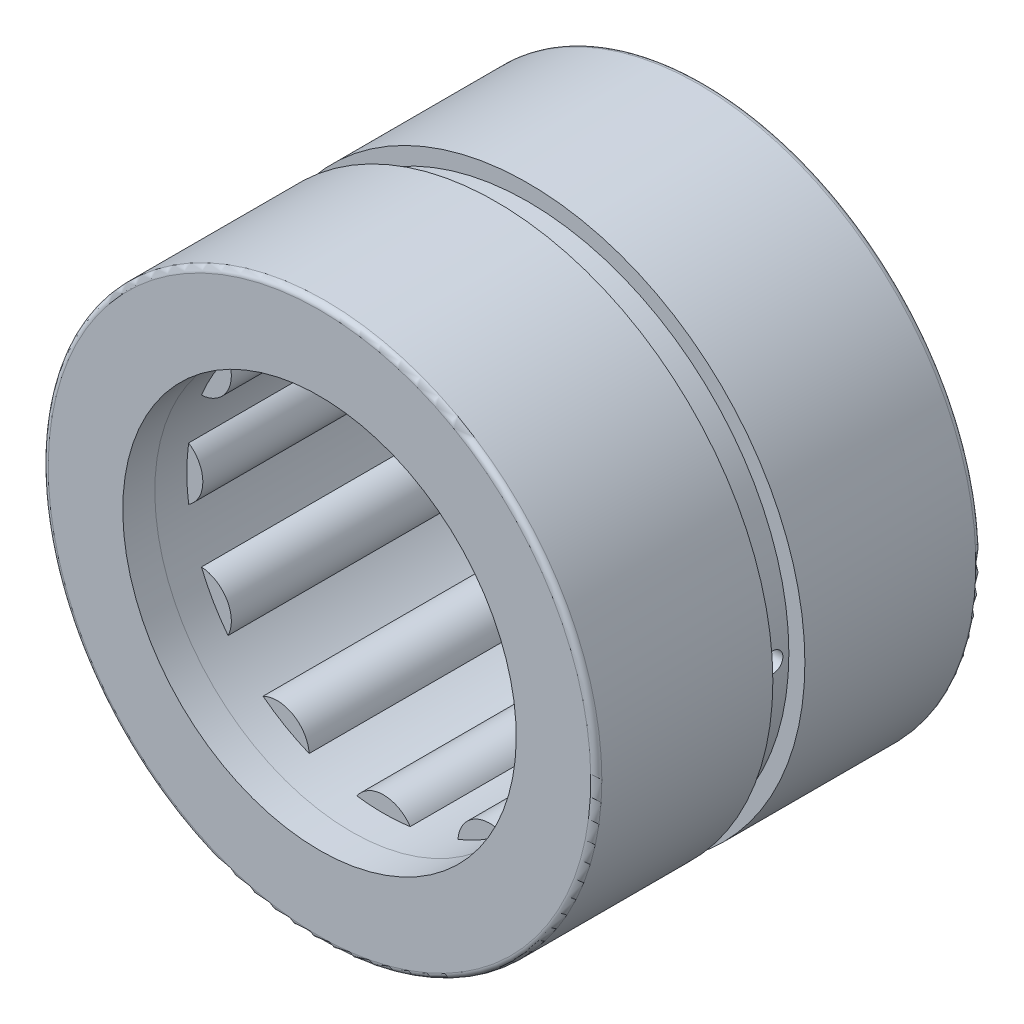
SolidWorks part; units mm, degrees
material "Plain Carbon Steel"
ref_plane "Front Plane" through (0, 0, 0) normal (0, 0, 1) x (1, 0, 0)
ref_plane "Top Plane" through (0, 0, 0) normal (0, 1, 0) x (1, 0, 0)
ref_plane "Right Plane" through (0, 0, 0) normal (1, 0, 0) x (0, 0, -1)
sketch "Sketch1" plane through (0, 0, 0) normal (1, 0, 0) x (0, 0, -1)
  line L0 (-8, 0) -> (8, 0) construction
  line L1 (0, 0) -> (0, 11.5) construction
  line L2 (-8, 0) -> (-8, 11.5) construction
  line L3 (-8, 11.5) -> (8, 11.5)
  line L4 (8, 11.5) -> (8, 0) construction
  line L5 (8, 0) -> (6.6693, 0) construction
  line L6 (6.6693, 0) -> (6.6693, 10.1693) construction
  line L7 (6.6693, 10.1693) -> (-6.6693, 10.1693)
  line L8 (-6.6693, 10.1693) -> (-6.6693, 0) construction
  line L9 (-6.6693, 0) -> (-8, 0) construction
  line L10 (-8, 11.5) -> (-8, 8.1733)
  line L11 (-8, 8.1733) -> (-6.6693, 8.1733)
  line L12 (-6.6693, 8.1733) -> (-6.6693, 10.1693)
  line L13 (6.6693, 11.5) -> (6.6693, 10.1693) construction
  line L14 (6.6693, 10.1693) -> (6.6693, 8.1733)
  line L15 (6.6693, 8.1733) -> (8, 8.1733)
  line L16 (8, 8.1733) -> (8, 11.5)
  line L17 (6.6693, 10.1693) -> (6.6693, 8.8387) construction
  line L18 (6.6693, 8.8387) -> (6.6693, 7.508) construction
  line L19 (6.6693, -10.1693) -> (6.6693, -8.8387) construction
  line L20 (6.6693, -11.5) -> (6.6693, -10.1693) construction
  line L21 (8, -8.1733) -> (8, -11.5) construction
  line L22 (6.6693, -8.1733) -> (8, -8.1733) construction
  line L23 (6.6693, -10.1693) -> (6.6693, -8.1733) construction
  line L24 (-6.6693, -8.1733) -> (-6.6693, -10.1693) construction
  line L25 (-8, -8.1733) -> (-6.6693, -8.1733) construction
  line L26 (-8, -11.5) -> (-8, -8.1733) construction
  line L27 (6.6693, -10.1693) -> (-6.6693, -10.1693) construction
  line L28 (-8, -11.5) -> (8, -11.5) construction
  point P5 (0, 7.508)
  dimension "Width" = 16
  dimension "OD" = 23
  dimension "Shaft Dia" = 15.016
revolve "Revolve1" add sketch "Sketch1" angle 360 about L0
sketch "Sketch2" plane through (0, 0, 0) normal (1, 0, 0) x (0, 0, -1)
  line L0 (6.6693, 10.1693) -> (-6.6693, 10.1693) construction
  line L1 (-5.3387, 8.8387) -> (5.3387, 8.8387) construction
  line L2 (-5.3387, 8.8387) -> (-5.3387, 10.1693) construction
  line L3 (-5.3387, 10.1693) -> (5.3387, 10.1693)
  line L4 (5.3387, 8.8387) -> (5.3387, 10.1693) construction
  line L5 (6.6693, 8.1733) -> (8, 8.1733) construction
  line L6 (-6.6693, 8.8387) -> (-5.3387, 8.8387) construction
  line L7 (5.3387, 8.8387) -> (6.6693, 8.8387) construction
  line L8 (-8, 8.1733) -> (-6.6693, 8.1733) construction
  line L9 (-5.3387, 9.1713) -> (-5.3387, 8.506) construction
  line L10 (-6.6693, 8.8387) -> (-6.6693, 8.1733) construction
  line L11 (-5.3387, 10.1693) -> (-5.3387, 9.1713)
  line L12 (5.3387, 10.1693) -> (5.3387, 9.1713)
  line L13 (5.3387, 9.1713) -> (-5.3387, 9.1713)
  line L14 (0, 10.1693) -> (0, 7.508) construction
  line L15 (-6.6693, 8.1733) -> (-6.6693, 10.1693) construction
  line L16 (-5.3387, 8.506) -> (-6.6693, 8.506) construction
  line L17 (0, 0) -> (8, 0) construction
  line L18 (8, -11.5) -> (8, 11.5) construction
  line L19 (-5.3387, -8.506) -> (-6.6693, -8.506) construction
  line L20 (0, -10.1693) -> (0, -7.508) construction
  line L21 (-6.6693, -8.8387) -> (-6.6693, -8.1733) construction
  line L22 (-5.3387, -9.1713) -> (-5.3387, -8.506) construction
  line L23 (5.3387, -8.8387) -> (6.6693, -8.8387) construction
  line L24 (-6.6693, -8.8387) -> (-5.3387, -8.8387) construction
  line L25 (5.3387, -8.8387) -> (5.3387, -10.1693) construction
  line L26 (-5.3387, -8.8387) -> (-5.3387, -10.1693) construction
  line L27 (-5.3387, -8.8387) -> (5.3387, -8.8387) construction
  line L28 (5.3387, -9.1713) -> (-5.3387, -9.1713) construction
  line L29 (5.3387, -10.1693) -> (5.3387, -9.1713) construction
  line L30 (-5.3387, -10.1693) -> (-5.3387, -9.1713) construction
  line L31 (-5.3387, -10.1693) -> (5.3387, -10.1693) construction
  line L32 (-6.6693, 10.1693) -> (-6.6693, 0) construction
  point P16 (0, 8.8387)
revolve "Revolve2" add sketch "Sketch2" angle 360 about L1
sketch "Sketch3" plane through (0, 0, 0) normal (1, 0, 0) x (0, 0, -1)
  line L0 (6.6693, 10.1693) -> (6.6693, 8.1733) construction
  line L1 (-6.6693, 8.8387) -> (6.6693, 8.8387)
  line L2 (-6.6693, 8.8387) -> (-6.6693, 9.1713)
  line L3 (-6.6693, 9.1713) -> (6.6693, 9.1713)
  line L4 (6.6693, 8.8387) -> (6.6693, 9.1713)
  line L5 (0, 0) -> (8, 0) construction
  line L6 (8, -11.5) -> (8, 11.5) construction
  line L7 (6.6693, -8.8387) -> (6.6693, -9.1713) construction
  line L8 (-6.6693, -9.1713) -> (6.6693, -9.1713) construction
  line L9 (-6.6693, -8.8387) -> (-6.6693, -9.1713) construction
  line L10 (-6.6693, -8.8387) -> (6.6693, -8.8387) construction
revolve "Revolve3" add sketch "Sketch3" angle 360 about L1
ref_axis "Axis1" through (0, 0, -8) along (0, 0, 1)
pattern_circular "CirPattern1" count 12 every 30 about axis through (0, 0, -8) along (0, 0, 1) of bodies 167 166
fillet "Fillet1" radius 0.23 2 edges at (0, -11.5, -8) (0, -11.5, 8)
sketch "Sketch4" plane through (0, 0, 0) normal (1, 0, 0) x (0, 0, -1)
  line L0 (-0.6653, 11.5) -> (0, 10.8347)
  line L1 (-8, 11.5) -> (8, 11.5) construction
  line L2 (0, 0) -> (0, 11.5) construction
  line L3 (0, 10.8347) -> (0.6653, 11.5)
  line L4 (0.6653, 11.5) -> (-0.6653, 11.5)
  line L5 (0, 11.5) -> (0, 10.1693) construction
revolve "Cut-Revolve1" cut sketch "Sketch4" angle 360 about L0
sketch "Sketch5" plane through (0, 0, -6.6693) normal (0, 0, 1) x (1, 0, 0)
  circle A0 centre (0, 0) radius 8.1733 construction
  circle A1 centre (0, 0) radius 10.1693
  circle A2 centre (0, 0) radius 10.1693 construction
  circle A3 centre (0, 0) radius 8.1733
  circle A4 centre (0, 0) radius 10.2693
  dimension "D1" = 0
  dimension "D2" = 0.1
extrude "Boss-Extrude1" add sketch "Sketch5" along normal up to surface (13.3387 mm away) separate body up to face at (0, -10.1693, 6.6693)
revolve "Cut-Revolve3" cut sketch "Sketch2<4>" angle 360 about L1
sketch "Sketch2<4>" plane through (0, 0, 0) normal (1, 0, 0) x (0, 0, -1) same geometry as "Sketch2"
pattern_circular "CirPattern2" count 12 over 360 about axis through (0, 0, 35.7154) along (0, 0, -1) of "Cut-Revolve3"
sketch "Sketch7" plane through (0, 0, 0) normal (1, 0, 0) x (0, 0, -1)
  line L0 (-0.6653, 11.5) -> (-0.6653, 10.8347)
  line L1 (-0.6653, 11.5) -> (-0.6653, -11.5) construction
  line L2 (-0.6653, 10.8347) -> (0.6653, 10.8347)
  line L3 (0.6653, 11.5) -> (0.6653, -11.5) construction
  line L4 (0.6653, 10.8347) -> (0.6653, 11.5)
  line L5 (0.6653, 11.5) -> (-0.6653, 11.5)
  dimension "D1" = 1.3307
revolve "Cut-Revolve4" cut sketch "Sketch7" angle 360 about axis through (0, 0, 35.7154) along (0, 0, -1)
sketch "Sketch8" plane through (0, 0, 0) normal (1, 0, 0) x (0, 0, -1)
  circle A0 centre (0, 0) radius 0.4167
  dimension "D1" = 0.6653
extrude "Cut-Extrude2" cut sketch "Sketch8" along normal through all
equation "\"Angle@CirPattern1\" = 360/\"Rollers@CirPattern1\""
equation "\"Rollers@CirPattern1\" = \"OD@Sketch1\"*.5"
equation "\"D1@Fillet1\" = \"OD@Sketch1\"*.01"
equation "\"D1@CirPattern2\"= \"Rollers@CirPattern1\""
equation "\"D1@Sketch8\"=\"D1@Sketch7\" * .5"
